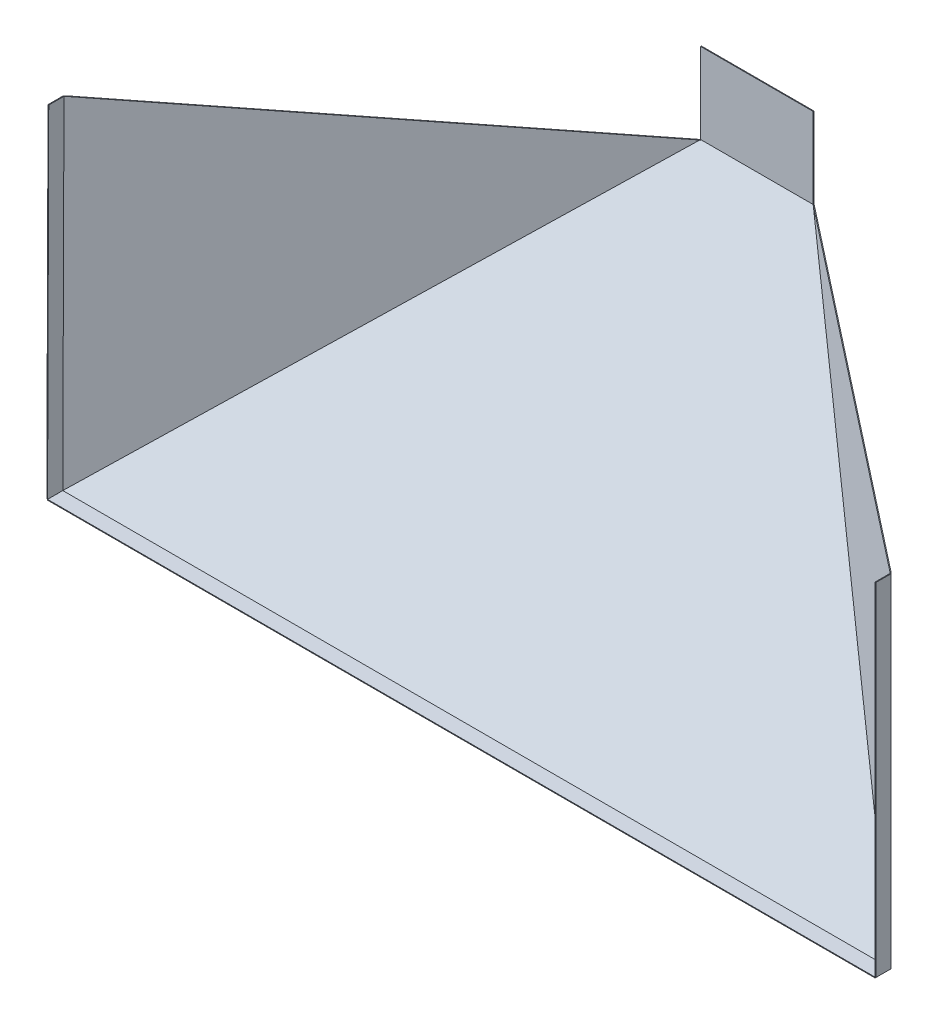
SolidWorks part; units mm, degrees
ref_plane "Front Plane" through (0, 0, 0) normal (0, 0, 1) x (1, 0, 0)
ref_plane "Top Plane" through (0, 0, 0) normal (0, 1, 0) x (1, 0, 0)
ref_plane "Right Plane" through (0, 0, 0) normal (1, 0, 0) x (0, 0, -1)
sketch "Sketch1" plane through (0, 0, 0) normal (0, 1, 0) x (1, 0, 0)
  line L1 (-544, 10) -> (544, 10)
  line L2 (-544, 10) -> (-544, -10)
  line L3 (-544, -10) -> (544, -10)
  line L4 (544, 10) -> (544, -10)
  line L5 (-544, 10) -> (544, -10) construction
  line L6 (-544, -10) -> (544, 10) construction
  point P0 (0, 0)
  dimension "D1" = 1088
  dimension "D2" = 20
extrude "Boss-Extrude1" add sketch "Sketch1" along normal blind 1
sketch "Sketch4" plane through (-544, 0, 0) normal (-1, 0, 0) x (0, 0, 1)
  line L0 (-10, 0) -> (-10, 1)
  line L1 (-10, 1) -> (-10.7738, 0.3666)
  arc A0 (-10.7738, 0.3666) -> (-10, 0) centre (-10, 1) ccw
  line M6 (-10, 1) -> (-10, 0)
  dimension "D1" = 1
  dimension "D2" = 50.7
extrude "Boss-Extrude4" add sketch "Sketch4" along direction (-1, 0, 0) on the side against the normal blind 1088 contours L1 A0 M6
sketch "Sketch5" plane through (0, 5.5002, -4.5018) normal (0, 0.7738, -0.6334) x (1, 0, 0)
  line L1 (-544, 7.105) -> (544, 7.105)
  line L2 (-544, 7.105) -> (-544, 8.105)
  line L3 (-544, 8.105) -> (544, 8.105)
  line L4 (544, 7.105) -> (544, 8.105)
extrude "Boss-Extrude5" add sketch "Sketch5" along normal blind 582
sketch "Sketch6" plane through (544, 0, 0) normal (1, 0, 0) x (0, 0, -1)
  line L0 (378.6277, 451.375) -> (379.6277, 451.375)
  line L1 (378.6277, 451.375) -> (379.4015, 450.7416) construction
  line L2 (379.4015, 450.7416) -> (378.6277, 451.375)
  arc A0 (379.6277, 451.375) -> (379.4015, 450.7416) centre (378.6277, 451.375) cw
  dimension "D1" = 1
  dimension "D2" = 39.3
extrude "Boss-Extrude6" add sketch "Sketch6" against normal blind 1088
sketch "Sketch7" plane through (0, 451.375, 0) normal (0, 1, 0) x (1, 0, 0)
  line L0 (-544, 378.6277) -> (544, 378.6277) construction
  line L1 (74, 378.6277) -> (-74, 378.6277)
  line L2 (74, 378.6277) -> (74, 379.6277)
  line L3 (74, 379.6277) -> (-74, 379.6277)
  line L4 (-74, 378.6277) -> (-74, 379.6277)
  line L5 (-544, 379.6277) -> (544, 379.6277) construction
  dimension "D1" = 148
  dimension "D2" = 470
  dimension "D3" = 470
extrude "Boss-Extrude7" add sketch "Sketch7" along normal blind 106
sketch "Sketch8" plane through (0, -4.5002, -5.4982) normal (0, 0.6334, 0.7738) x (1, 0, 0)
  line L0 (74, 589.1076) -> (544, 7.1076)
  line L1 (544, 7.1076) -> (544, 589.1076)
  line L2 (544, 589.1076) -> (74, 589.1076)
  line L3 (-74, 589.1076) -> (74, 589.1076) construction
  line L4 (74, 589.1076) -> (544, 589.1076) construction
  line L5 (-74, 589.1076) -> (-544, 7.1076)
  line L6 (-544, 7.1076) -> (-544, 589.1076)
  line L7 (-544, 589.1076) -> (-74, 589.1076)
extrude "Cut-Extrude3" cut sketch "Sketch8" against normal blind 148
sketch "Sketch13" plane through (0, 451.375, 0) normal (0, 1, 0) x (1, 0, 0)
  line L1 (544, 378.6277) -> (74, 378.6277)
  line L2 (544, 378.6277) -> (544, 379.6277)
  line L3 (544, 379.6277) -> (74, 379.6277)
  line L4 (74, 378.6277) -> (74, 379.6277)
  line L5 (-544, 378.6277) -> (-74, 378.6277)
  line L6 (-544, 378.6277) -> (-544, 379.6277)
  line L7 (-544, 379.6277) -> (-74, 379.6277)
  line L8 (-74, 378.6277) -> (-74, 379.6277)
revolve "Cut-Revolve1" cut sketch "Sketch13" angle 39.3 about L5
sketch3d "3DSketch8"
  line L0 (-74, 450.7416, -379.4015) -> (-74, 451.375, -378.6277) construction
  line L1 (-74, 450.7416, -379.4015) -> (-74, 451.375, -378.6277)
  line L2 (-74, 451.375, -378.6277) -> (-74.6184, 451.3772, -379.4135)
  arc A0 (-74.6184, 451.3772, -379.4135) -> (-74, 450.7416, -379.4015) centre (-74, 451.375, -378.6277) cw
  point P8 (-74.6283, 450.773, -378.1349)
  dimension "D1" = 1
  dimension "D2" = 52.645
extrude "Boss-Extrude11" add sketch "3DSketch8" along direction (0.6283, 0.602, -0.4928) on the side of the normal blind 748.0802
sketch "Sketch17" plane through (-119.8301, 202.6926, 94.8586) normal (-0.472, 0.7985, 0.3737) x (0.881, 0.4421, 0.1684)
  line L0 (-480.5271, 26.2481) -> (-481.2034, 26.9848)
  line L1 (-480.5271, 26.2481) -> (70.5614, 532.1033)
  line L2 (-481.2034, 26.9848) -> (69.8852, 532.84)
  line L3 (70.5614, 532.1033) -> (69.8852, 532.84)
  line L4 (69.8852, 532.84) -> (69.9028, 532.8562)
  line L5 (69.9028, 532.8562) -> (70.5791, 532.1195)
  line L6 (70.5791, 532.1195) -> (70.5614, 532.1033)
  line M1 (-481.2034, 26.9848) -> (-480.5271, 26.2481)
  line M2 (-480.5271, 26.2481) -> (70.5791, 532.1195)
  line M3 (70.5791, 532.1195) -> (69.9028, 532.8562)
  line M4 (69.9028, 532.8562) -> (-481.2034, 26.9848)
extrude "Boss-Extrude12" add sketch "Sketch17" along normal blind 800 contours L3 M2 M3 M4 | L3 M2 M4 M1
sketch "Sketch18" plane through (0, 1, 0) normal (0, 1, 0) x (1, 0, 0)
  line L0 (544, 10) -> (-544, 10) construction
  line L1 (-488.708, 10) -> (-1058.7294, 10)
  line L2 (-488.708, 10) -> (-488.708, -377.1528)
  line L3 (-488.708, -377.1528) -> (-1058.7294, -377.1528)
  line L4 (-1058.7294, 10) -> (-1058.7294, -377.1528)
  dimension "D1" = 0
extrude "Cut-Extrude5" cut sketch "Sketch18" along normal through all
sketch3d "3DSketch9"
  line L1 (-74, 450.7416, -379.4015) -> (-855.746, 450.7416, -379.4015)
  line L2 (-74, 450.7416, -379.4015) -> (-74, 1127.3387, -379.4015)
  line L3 (-74, 1127.3387, -379.4015) -> (-855.746, 1127.3387, -379.4015)
  line L4 (-855.746, 450.7416, -379.4015) -> (-855.746, 1127.3387, -379.4015)
extrude "Cut-Extrude6" cut sketch "3DSketch9" along a picked direction on the side of the normal blind 800 and the other way blind 10
sketch3d "3DSketch11"
  line L1 (74, 450.7416, -379.4015) -> (74, 451.375, -378.6277)
  line L2 (74, 451.375, -378.6277) -> (74.6172, 451.3751, -379.4145)
  arc A0 (74.6172, 451.3751, -379.4145) -> (74, 450.7416, -379.4015) centre (74, 451.375, -378.6277) ccw
  point P8 (73.3717, 451.977, -379.1204)
  dimension "D1" = 1
  dimension "D2" = 52.5
extrude "Boss-Extrude13" add sketch "3DSketch11" along direction (0.6283, -0.602, 0.4928) on the side against the normal blind 748.0802
sketch "Sketch20" plane through (120.6412, 203.3899, 94.6766) normal (0.4736, 0.7985, 0.3717) x (0.8807, -0.4308, -0.1968)
  line L0 (-54.0613, 534.2795) -> (-54.7597, 533.5637)
  line L1 (-54.0613, 534.2795) -> (481.3478, 11.8315)
  line L2 (-54.7597, 533.5637) -> (480.6494, 11.1158)
  line L3 (481.3478, 11.8315) -> (480.6494, 11.1158)
extrude "Boss-Extrude14" add sketch "Sketch20" along normal blind 748.0802
sketch "Sketch21" plane through (0, 1, 0) normal (0, 1, 0) x (1, 0, 0)
  line L0 (544, 10) -> (-544, 10) construction
  line L1 (512.5033, 10) -> (989.3621, 10)
  line L2 (512.5033, 10) -> (512.5033, -315.6472)
  line L3 (512.5033, -315.6472) -> (989.3621, -315.6472)
  line L4 (989.3621, 10) -> (989.3621, -315.6472)
  dimension "D1" = 0
extrude "Cut-Extrude7" cut sketch "Sketch21" along a picked direction on the side of the normal through all
sketch3d "3DSketch12"
  line L0 (74, 450.7416, -379.4015) -> (-74, 450.7416, -379.4015) construction
  line L2 (74, 450.7416, -379.4015) -> (907.5511, 450.7416, -379.4015)
  line L3 (74, 450.7416, -379.4015) -> (74, 1222.3252, -379.4015)
  line L4 (74, 1222.3252, -379.4015) -> (907.5511, 1222.3252, -379.4015)
  line L5 (907.5511, 450.7416, -379.4015) -> (907.5511, 1222.3252, -379.4015)
extrude "Cut-Extrude9" cut sketch "3DSketch12" along a picked direction on the side against the normal through all and the other way blind 10
sketch "Sketch23" plane through (0, 0, -10) normal (0, 0, 1) x (1, 0, 0)
  line L0 (544, 1.0103) -> (543.8993, 450.7416)
  line L1 (544, 1.0103) -> (545, 1.0105)
  line L2 (543.8993, 450.7416) -> (544.8993, 450.7418)
  line L3 (545, 1.0105) -> (544.8993, 450.7418)
  dimension "D1" = 1
extrude "Boss-Extrude15" add sketch "Sketch23" along normal blind 20
fillet "Fillet1" radius 10 1 edges at (545.5696, 226.7211, -10)
sketch "Sketch26" plane through (0, 0, -10) normal (0, 0, 1) x (1, 0, 0)
  line L0 (-542.4267, 450.7416) -> (-543.9999, 1.0201)
  line L1 (-542.4267, 450.7416) -> (-543.4267, 450.7451)
  line L2 (-543.9999, 1.0201) -> (-544.9999, 1.0236)
  line L3 (-543.4267, 450.7451) -> (-544.9999, 1.0236)
  line L4 (-544, 1) -> (-542.4267, 450.7416) construction
  dimension "D1" = 1
extrude "Boss-Extrude20" add sketch "Sketch26" along normal blind 20
fillet "Fillet2" radius 10 1 edges at (-544.8274, 226.7115, -10)
